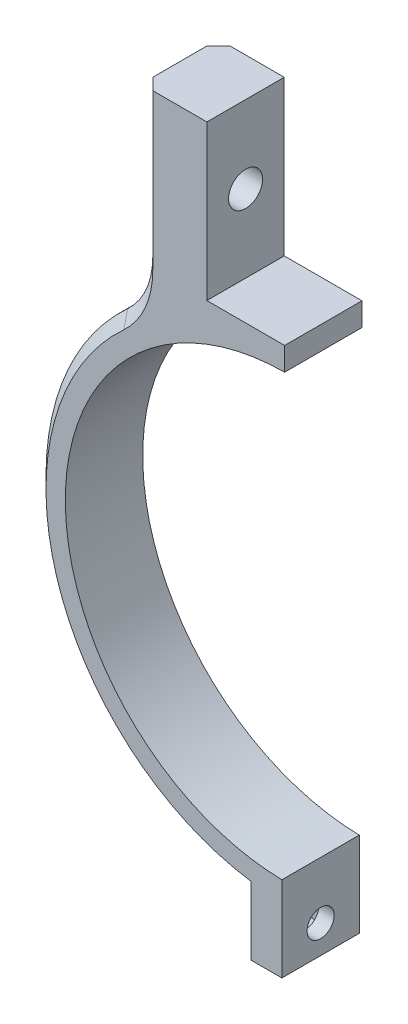
SolidWorks part; units mm, degrees
ref_plane "Ebene vorne" through (0, 0, 0) normal (0, 0, 1) x (1, 0, 0)
ref_plane "Ebene oben" through (0, 0, 0) normal (0, 1, 0) x (1, 0, 0)
ref_plane "Ebene rechts" through (0, 0, 0) normal (1, 0, 0) x (0, 0, -1)
sketch "Skizze1" plane through (0, 0, 0) normal (0, 0, 1) x (1, 0, 0)
  line L0 (0, 0) -> (0, 53.7291) construction
  line L14 (0, 0) -> (0, -44.1347) construction
  line L15 (0.5, -28.4956) -> (0.5, -32.4962)
  line L16 (-0.5, -28.4956) -> (-0.5, -32.4962)
  line L17 (0.5, -32.4962) -> (0.5, -39.4962)
  line L18 (0.5, -39.4962) -> (4.5, -39.4962)
  line L19 (4.5, -39.4962) -> (4.5, -32.187)
  line L20 (-4.5, -39.4962) -> (-4.5, -32.187)
  line L21 (-0.5, -39.4962) -> (-4.5, -39.4962)
  line L22 (-0.5, -32.4962) -> (-0.5, -39.4962)
  line L23 (-10.2, 31.5) -> (-10.2, 51.5)
  line L24 (-10.2, 51.5) -> (-18.7, 51.5)
  line L25 (-18.7, 51.5) -> (-18.7, 26.5812)
  line L26 (-10.2, 31.5) -> (10.2, 31.5)
  line L27 (0, 28.5) -> (12.0002, 28.5) construction
  line L28 (18.7, 51.5) -> (18.7, 26.5812)
  line L29 (10.2, 51.5) -> (18.7, 51.5)
  line L30 (10.2, 31.5) -> (10.2, 51.5)
  arc A0 (0.5, -28.4956) -> (-0.5, -28.4956) centre (0, 0) ccw
  arc A1 (-18.7, 26.5812) -> (-4.5, -32.187) centre (0, 0) ccw
  arc A2 (4.5, -32.187) -> (18.7, 26.5812) centre (0, 0) ccw
  point P10 (0, 33.5025)
  point P11 (0, 31.6594)
  point P17 (0, 31.5)
  point P18 (0, 39.6025)
  dimension "D1" = 57
  dimension "D2" = 4
  dimension "D3" = 20.4
  dimension "D4" = 20
  dimension "D5" = 3
  dimension "D6" = 8.5
  dimension "D10" = 1
  dimension "D11" = 4
  dimension "D12" = 7
extrude "Aufsatz-Linear austragen1" add sketch "Skizze1" along normal blind 10
sketch "Skizze2" plane through (-4.5, 0, 0) normal (-1, 0, 0) x (0, 0, 1)
  line L0 (0, -35.8416) -> (10, -35.8416) construction
  line L1 (0, -32.187) -> (0, -39.4962) construction
  line L2 (10, -32.187) -> (10, -39.4962) construction
  circle A0 centre (5, -35.8416) radius 1.75
  dimension "D1" = 3.5
extrude "Schnitt-Linear austragen1" cut sketch "Skizze2" against normal through all
sketch "Skizze3" plane through (0, 0, 10) normal (0, 0, 1) x (1, 0, 0)
  line L0 (-10.8174, 36.4205) -> (0, 26.8755)
  line L1 (0, 26.8755) -> (11.8484, 37.1414)
  line L2 (11.8484, 37.1414) -> (47.3746, 17.8863)
  line L3 (47.3746, 17.8863) -> (51.4546, -59.0738)
  line L4 (51.4546, -59.0738) -> (-81.1349, -43.2704)
  line L5 (-81.1349, -43.2704) -> (-40.9452, 68.8874)
  line L6 (-40.9452, 68.8874) -> (-10.8174, 36.4205)
extrude "Schnitt-Linear austragen2" [suppressed] cut sketch "Skizze3" against normal through all
sketch "Skizze4" plane through (-18.7, 0, 0) normal (-1, 0, 0) x (0, 0, 1)
  line L0 (5, 51.5) -> (5, 31.5) construction
  line L1 (10, 51.5) -> (0, 51.5) construction
  line L3 (10, 31.5) -> (0, 31.5) construction
  circle A0 centre (5, 41.5) radius 2.2
  dimension "D1" = 4.4
extrude "Schnitt-Linear austragen3" cut sketch "Skizze4" against normal through all
fillet "Verrundung1" radius 10 2 edges at (18.7, 26.5812, 5) (-18.7, 26.5812, 5)
sketch "Skizze5" plane through (-4.5, 0, 0) normal (-1, 0, 0) x (0, 0, 1)
  line L1 (2.25, -38.5916) -> (7.75, -38.5916)
  line L2 (2.25, -38.5916) -> (2.25, -33.0916)
  line L3 (2.25, -33.0916) -> (7.75, -33.0916)
  line L4 (7.75, -38.5916) -> (7.75, -33.0916)
  line L5 (2.25, -38.5916) -> (7.75, -33.0916) construction
  line L6 (2.25, -33.0916) -> (7.75, -38.5916) construction
  point P0 (5, -35.8416)
  dimension "D1" = 5.5
extrude "Schnitt-Linear austragen4" cut sketch "Skizze5" against normal blind 2
chamfer "Fase1" distance 1.5 angle 45 12 edges at (-18.7, 41.4229, 0) (-19.5477, 27.3165, 0) (-31.0366, -9.6425, 0) (18.7, 41.4229, 0) (19.5477, 27.3165, 0) (31.0366, -9.6425, 0) (-18.7, 41.4229, 10) (-19.5477, 27.3165, 10) (-31.0366, -9.6425, 10) (18.7, 41.4229, 10) (19.5477, 27.3165, 10) (31.0366, -9.6425, 10)
sketch "Skizze6" plane through (0, 0, 0) normal (0, 0, 1) x (1, 0, 0)
  line L0 (0, -80.0659) -> (0, 27.4786)
  line L1 (0, 80.0659) -> (51.6949, 80.0659)
  line L2 (51.6949, 80.0659) -> (51.6949, -72.9797)
  line L3 (51.6949, -72.9797) -> (0, -80.0659)
  line L4 (0, 27.4786) -> (-0.15, 27.4786)
  line L5 (-0.15, 27.4786) -> (-0.15, 32.4289)
  line L6 (-0.15, 32.4289) -> (0, 32.4289)
  line L7 (0, 32.4289) -> (0, 80.0659)
  point P4 (0, 0)
  dimension "D1" = 0.15
extrude "Schnitt-Linear austragen5" cut sketch "Skizze6" along normal through all
